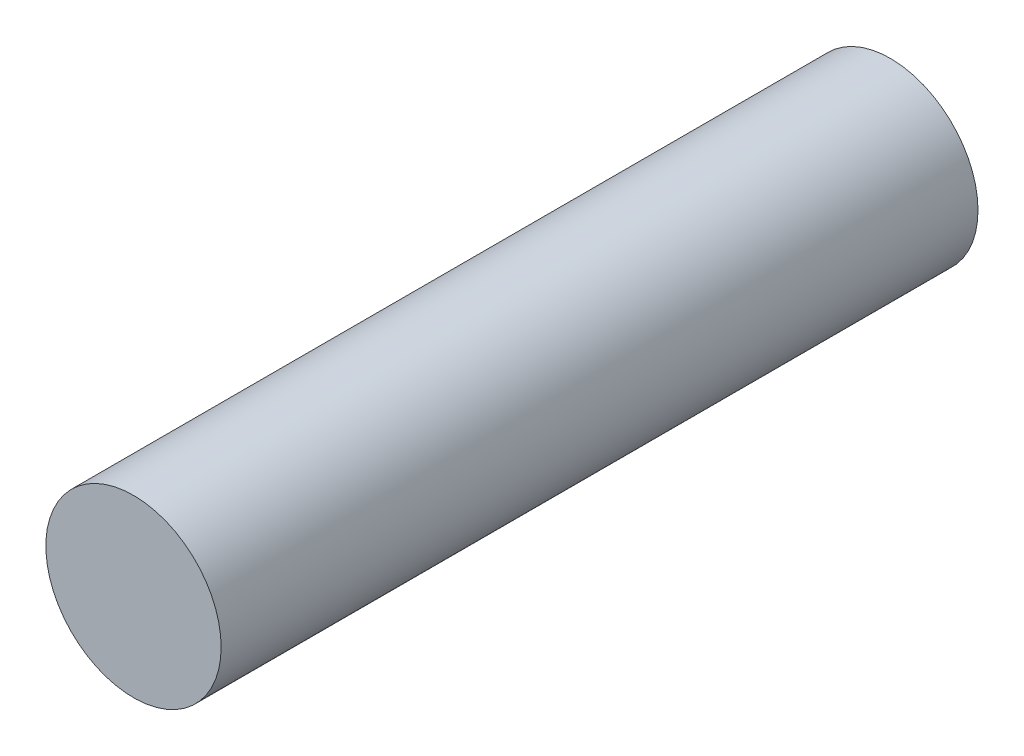
SolidWorks part; units mm, degrees
ref_plane "Front Plane" through (0, 0, 0) normal (0, 0, 1) x (1, 0, 0)
ref_plane "Top Plane" through (0, 0, 0) normal (0, 1, 0) x (1, 0, 0)
ref_plane "Right Plane" through (0, 0, 0) normal (1, 0, 0) x (0, 0, -1)
sketch "Sketch1" plane through (0, 0, 0) normal (0, 0, 1) x (1, 0, 0)
  circle A0 centre (0, 0) radius 2.49
  dimension "D1" = 4.98
extrude "Boss-Extrude1" add sketch "Sketch1" along normal blind 8 and the other way blind 13.5
sketch "Sketch2" plane through (0, 0, 0) normal (0, 0, 1) x (1, 0, 0)
  circle A0 centre (0, 0) radius 2.5 construction
  dimension "D1" = 5
